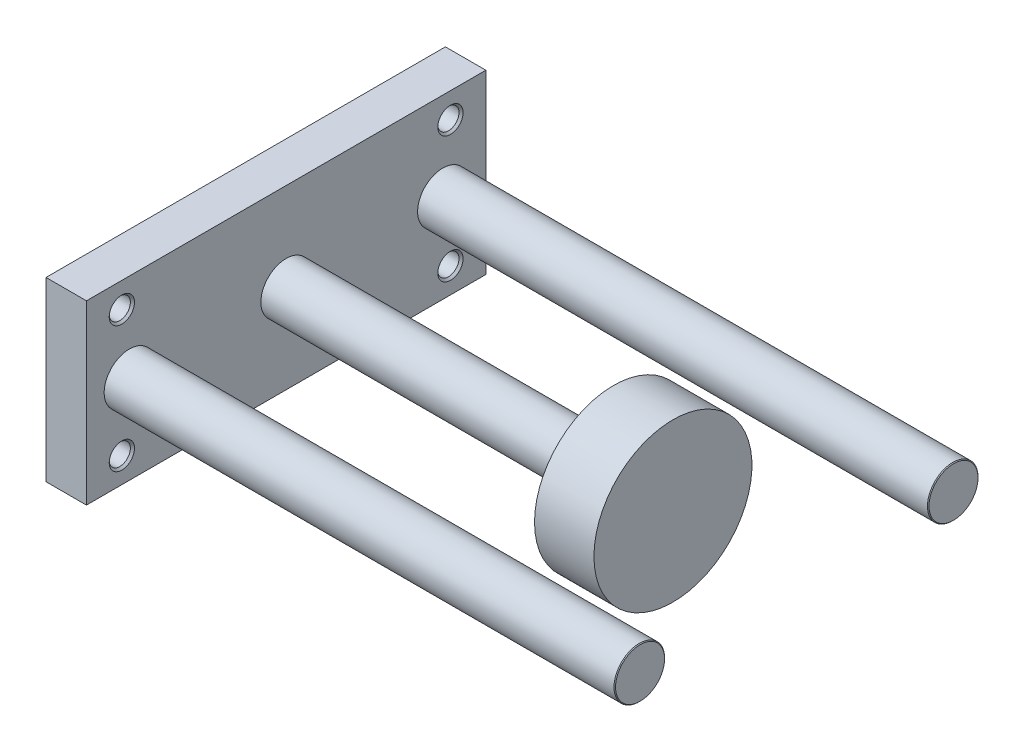
SolidWorks part; units mm, degrees
ref_plane "前视基准面" through (0, 0, 0) normal (0, 0, 1) x (1, 0, 0)
ref_plane "上视基准面" through (0, 0, 0) normal (0, 1, 0) x (1, 0, 0)
ref_plane "右视基准面" through (0, 0, 0) normal (1, 0, 0) x (0, 0, -1)
sketch "草图1" plane through (0, 0, 0) normal (1, 0, 0) x (0, 0, -1)
  line L0 (-79, -35) -> (79, -35)
  line L1 (79, -35) -> (79, 35)
  line L2 (79, 35) -> (-79, 35)
  line L3 (-79, 35) -> (-79, -35)
extrude "凸台-拉伸1" add sketch "草图1" along normal blind 16
ref_plane "基准面1" through (0, 0, 62) normal (0, 0, 1) x (1, 0, 0)
sketch "草图2" plane through (0, 0, 62) normal (0, 0, 1) x (1, 0, 0)
  line L0 (0, 9.25) -> (0, 7.5)
  line L1 (0.5, 8) -> (6.5, 8)
  line L2 (6.5, 8) -> (6.5, 9)
  line L3 (6.5, 9) -> (0.25, 9)
  line L4 (0.25, 9) -> (0, 9.25)
  line L5 (6.5, 0) -> (0, 0) construction
  arc A0 (0, 7.5) -> (0.5, 8) centre (0.5, 7.5) cw
revolve "切除-旋转1" cut sketch "草图2" angle 360 about L5 reverse direction yes
sketch "草图3" plane through (0, 0, 0) normal (1, 0, 0) x (0, 0, -1)
  line L0 (-62, 0) -> (62, 0)
pattern_linear "阵列(线性)1" count 3 spacing 62 along (0, 0, -1) of "切除-旋转1"
sketch "草图4" plane through (0, 0, 0) normal (0, 0, 1) x (1, 0, 0)
  line L0 (16, 0) -> (16, 10)
  line L1 (16, 10) -> (145.5, 10)
  line L2 (145.5, 10) -> (145.5, 31.25)
  line L3 (145.5, 31.25) -> (169, 31.25)
  line L4 (169, 31.25) -> (169, 0)
  line L5 (169, 0) -> (16, 0)
  line L6 (169, 0) -> (16, 0) construction
revolve "旋转1" add sketch "草图4" angle 360 about L6 reverse direction yes
ref_plane "基准面2" through (0, 0, 62) normal (0, 0, 1) x (1, 0, 0)
sketch "草图5" plane through (0, 0, 62) normal (0, 0, 1) x (1, 0, 0)
  line L0 (16, 0) -> (16, 10)
  line L1 (16, 10) -> (217.7, 10)
  line L2 (217.7, 10) -> (218, 9.7)
  line L3 (218, 9.7) -> (218, 0)
  line L4 (218, 0) -> (16, 0)
  line L5 (218, 0) -> (16, 0) construction
revolve "旋转2" add sketch "草图5" angle 360 about L5 reverse direction yes
ref_plane "基准面3" through (0, 0, -62) normal (0, 0, 1) x (1, 0, 0)
sketch "草图6" plane through (0, 0, -62) normal (0, 0, 1) x (1, 0, 0)
  line L0 (16, 0) -> (16, 10)
  line L1 (16, 10) -> (217.7, 10)
  line L2 (217.7, 10) -> (218, 9.7)
  line L3 (218, 9.7) -> (218, 0)
  line L4 (218, 0) -> (16, 0)
  line L5 (218, 0) -> (16, 0) construction
revolve "旋转3" add sketch "草图6" angle 360 about L5 reverse direction yes
ref_plane "基准面4" through (0, 0, 65) normal (0, 0, 1) x (1, 0, 0)
sketch "草图7" plane through (0, 0, 65) normal (0, 0, 1) x (1, 0, 0)
  line L0 (0, -25) -> (0, -20)
  line L1 (0, -20) -> (0.812, -20.812)
  line L2 (0.812, -20.812) -> (15.188, -20.812)
  line L3 (15.188, -20.812) -> (16, -20)
  line L4 (16, -20) -> (16, -25)
  line L5 (16, -25) -> (0, -25)
  line L6 (16, -25) -> (0, -25) construction
revolve "切除-旋转2" cut sketch "草图7" angle 360 about L6 reverse direction yes
cosmetic thread "装饰螺纹线1" parameters "D1"=16, "D2"=10
sketch "草图8" plane through (0, 0, 0) normal (1, 0, 0) x (0, 0, -1)
  line L0 (-65, -25) -> (65, -25)
  line L1 (-65, -25) -> (-65, 25)
pattern_linear "阵列(线性)2" count 2 spacing 130 along (0, 0, -1) count 2 spacing 50 along (0, 1, 0) of "切除-旋转2"
ref_plane "基准面5" through (0, 0, 40) normal (0, 0, 1) x (1, 0, 0)
sketch "草图9" plane through (0, 0, 40) normal (0, 0, 1) x (1, 0, 0)
  line L0 (0, 0) -> (0, 2.5)
  line L1 (0, 2.5) -> (8, 2.5)
  line L2 (8, 2.5) -> (8, 0)
  line L3 (8, 0) -> (0, 0)
  line L4 (8, 0) -> (0, 0) construction
revolve "切除-旋转3" cut sketch "草图9" angle 360 about L4 reverse direction yes
ref_plane "基准面6" through (0, 0, -40) normal (0, 0, 1) x (1, 0, 0)
hole_wizard "孔1" positions "草图11" profile "草图10" legacy
sketch "草图11" plane through (0, 0, 0) normal (-1, 0, 0) x (0, 0, 1)
  point P0 (-40, 0)
sketch "草图10" plane through (0, 0, -40) normal (0, 1, 0) x (0, 0, 1)
  line L0 (0, 0) -> (0, 9.4434)
  line L1 (0, 9.4434) -> (2.5, 8)
  line L2 (2.5, 8) -> (2.5, 0)
  line L4 (2.5, 0) -> (0, 0)
  line L6 (0, 9.4434) -> (-2.5, 8) construction
  line L7 (0, -4.2442) -> (0, 117.3081) construction
  dimension "直径" = 5
  dimension "深度" = 8
  dimension "导头角度" = 120
sketch "草图12" plane through (0, 0, 0) normal (1, 0, 0) x (0, 0, -1)
  line L0 (39.7, -2.5) -> (40.3, -2.5)
  line L1 (40.3, 2.5) -> (39.7, 2.5)
  arc A0 (39.7, 2.5) -> (39.7, -2.5) centre (39.7, 0) ccw
  arc A1 (40.3, -2.5) -> (40.3, 2.5) centre (40.3, 0) ccw
extrude "切除-拉伸1" cut sketch "草图12" along normal blind 4
ref_plane "基准面7" through (16, 0, 0) normal (1, 0, 0) x (0, 0, -1)
ref_plane "基准面8" through (6, 0, 0) normal (1, 0, 0) x (0, 0, -1)
ref_plane "for_body XY" through (0, 0, 0) normal (1, 0, 0) x (0, 0, -1)
ref_plane "for_body XZ" through (0, 0, 0) normal (0, -1, 0) x (-1, 0, 0)
ref_plane "for_body YZ" through (0, 0, 0) normal (0, 0, -1) x (-1, 0, 0)
ref_axis "for_body X" through (0, 0, 80.9) along (0, 0, -1)
ref_axis "for_body Y" through (0, -50, 0) along (0, 1, 0)
ref_axis "for_body Z" through (80.9, 0, 0) along (-1, 0, 0)
sketch3d "for_body"
  point P0 (0, 0, 0)
ref_plane "for_rod XY" through (16, 0, 0) normal (-1, 0, 0) x (0, 0, 1)
ref_plane "for_rod XZ" through (0, 0, 0) normal (0, 1, 0) x (1, 0, 0)
ref_plane "for_rod YZ" through (0, 0, 0) normal (0, 0, -1) x (-1, 0, 0)
ref_axis "for_rod X" through (16, 0, 80.9) along (0, 0, -1)
ref_axis "for_rod Y" through (16, 50, 0) along (0, -1, 0)
ref_axis "for_rod Z" through (-80.9, 0, 0) along (1, 0, 0)
sketch3d "for_rod"
  point P0 (16, 0, 0)
ref_plane "screw XY" through (6, 0, 0) normal (-1, 0, 0) x (0, 0, 1)
ref_plane "screw XZ" through (0, 0, 0) normal (0, 1, 0) x (1, 0, 0)
ref_plane "screw YZ" through (0, 0, 0) normal (0, 0, -1) x (-1, 0, 0)
ref_axis "screw X" through (6, 0, 80.9) along (0, 0, -1)
ref_axis "screw Y" through (6, 50, 0) along (0, -1, 0)
ref_axis "screw Z" through (-80.9, 0, 0) along (1, 0, 0)
sketch3d "screw"
  point P0 (6, 0, 0)
